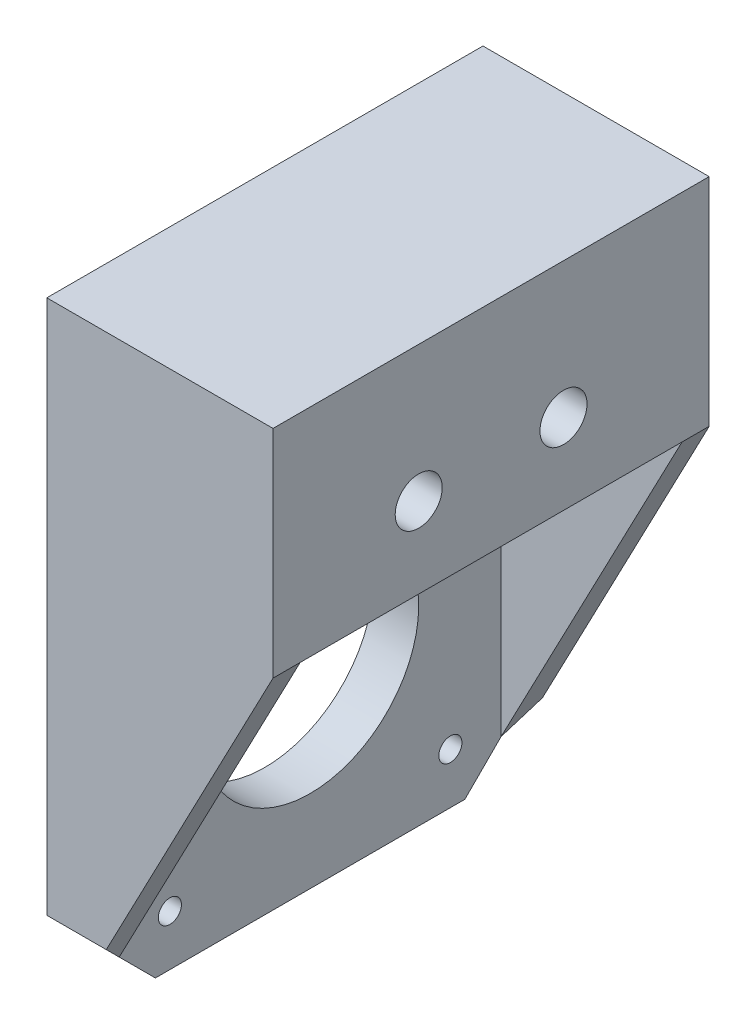
SolidWorks part; units mm, degrees
ref_plane "Front Plane" through (0, 0, 0) normal (0, 0, 1) x (1, 0, 0)
ref_plane "Top Plane" through (0, 0, 0) normal (0, 1, 0) x (1, 0, 0)
ref_plane "Right Plane" through (0, 0, 0) normal (1, 0, 0) x (0, 0, -1)
sketch "Sketch1" plane through (0, 0, 0) normal (1, 0, 0) x (0, 0, -1)
  line L0 (-0.3826, 8.0214) -> (-6.4826, 8.0214)
  line L1 (-6.4826, 8.0214) -> (-9.3826, 8.0214)
  line L2 (-9.3826, 8.0214) -> (-9.3826, -34.1786)
  line L3 (-9.3826, -34.1786) -> (-4.3816, -34.1786)
  line L4 (-4.3816, -34.1786) -> (-0.3826, -30.1796)
  line L5 (-0.3826, -30.1796) -> (-0.3826, 8.0214)
  line L6 (-6.4826, 25.8214) -> (-6.4826, 8.0214)
  line L7 (-6.4826, 8.0214) -> (-0.3826, 8.0214)
  line L8 (-0.3826, 8.0214) -> (2.6174, 8.0214)
  line L9 (2.6174, 8.0214) -> (2.6174, 25.8214)
  line L10 (2.6174, 25.8214) -> (-6.4826, 25.8214)
  circle A0 centre (-5.9826, -28.5786) radius 1.275
  circle A1 centre (-5.9826, 2.4214) radius 1.275
extrude "Boss-Extrude1" add sketch "Sketch1" along normal blind 5 contours L4 L5 L0 L1 L2 L3 A1 A0 | L9 L10 L6 L0 L8 region at (0, -12.6414, 4.9216) region at (0, 16.9214, 1.9326)
sketch "Sketch2" plane through (5, 0, 0) normal (1, 0, 0) x (0, 0, -1)
  line L1 (-6.4826, 25.8214) -> (2.6174, 25.8214)
  line L2 (-6.4826, 25.8214) -> (-6.4826, 8.0214)
  line L3 (-6.4826, 8.0214) -> (2.6174, 8.0214)
  line L4 (2.6174, 25.8214) -> (2.6174, 8.0214)
extrude "Boss-Extrude2" add sketch "Sketch2" along normal blind 20
sketch "Sketch3" plane through (0, 0, 0.3826) normal (0, 0, -1) x (-1, 0, 0)
  line L1 (-25, 8.0214) -> (0, 8.0214)
  line L2 (0, 8.0214) -> (0, -30.1796)
  line L3 (0, -30.1796) -> (-5, -30.1796)
  line L4 (-5, -30.1796) -> (-25, 8.0214)
extrude "Boss-Extrude3" add sketch "Sketch3" along normal blind 3
sketch "Sketch4" plane through (5, 0, 0) normal (1, 0, 0) x (0, 0, -1)
  line L0 (-0.3826, -30.1796) -> (2.6174, -27.1796)
  line L1 (2.6174, 8.0214) -> (2.6174, -30.1796) construction
  line L2 (2.6174, -27.1796) -> (2.6174, -30.1796)
  line L3 (2.6174, -30.1796) -> (-0.3826, -30.1796)
extrude "Cut-Extrude1" cut sketch "Sketch4" against normal mid plane 30
ref_plane "Plane2" through (0, 0, 21.4826) normal (0, 0, 1) x (1, 0, 0)
mirror "Mirror14" about plane through (0, 0, 21.4826) normal (0, 0, 1) of bodies 104 106
sketch "Sketch7" plane through (5, 0, 0) normal (1, 0, 0) x (0, 0, -1)
  line L1 (-33.5826, 8.0214) -> (-9.3826, 8.0214)
  line L2 (-33.5826, 8.0214) -> (-33.5826, -34.1786)
  line L3 (-33.5826, -34.1786) -> (-9.3826, -34.1786)
  line L4 (-9.3826, 8.0214) -> (-9.3826, -34.1786)
extrude "Boss-Extrude4" add sketch "Sketch7" against normal blind 5
sketch "Sketch8" plane through (5, 0, 0) normal (1, 0, 0) x (0, 0, -1)
  circle A0 centre (-21.4826, -13.0786) radius 12
extrude "Cut-Extrude3" cut sketch "Sketch8" against normal blind 5
sketch "Sketch10" plane through (25, 0, 0) normal (1, 0, 0) x (0, 0, -1)
  line L1 (-45.5826, 25.8214) -> (2.6174, 25.8214)
  line L2 (-45.5826, 25.8214) -> (-45.5826, 8.0214)
  line L3 (-45.5826, 8.0214) -> (2.6174, 8.0214)
  line L4 (2.6174, 25.8214) -> (2.6174, 8.0214)
extrude "Boss-Extrude5" add sketch "Sketch10" against normal blind 5
fillet "Fillet1" radius 3 2 edges at (20, 16.9214, 36.4826) (20, 16.9214, 6.4826)
sketch "Sketch12" plane through (0, 25.8214, 0) normal (0, 1, 0) x (1, 0, 0)
  line L8 (25, 2.6174) -> (0, 2.6174)
  line L9 (0, 2.6174) -> (0, -6.4826)
  line L10 (0, -6.4826) -> (17, -6.4826)
  line L11 (20, -9.4826) -> (20, -33.4826)
  line L12 (17, -36.4826) -> (0, -36.4826)
  line L13 (0, -36.4826) -> (0, -45.5826)
  line L14 (0, -45.5826) -> (25, -45.5826)
  line L15 (25, -45.5826) -> (25, 2.6174)
  line L16 (25, 2.6174) -> (0, 2.6174)
  line L17 (0, 2.6174) -> (0, -6.4826)
  line L18 (0, -6.4826) -> (17, -6.4826)
  line L19 (20, -9.4826) -> (20, -33.4826)
  line L20 (17, -36.4826) -> (0, -36.4826)
  line L21 (0, -36.4826) -> (0, -45.5826)
  line L22 (0, -45.5826) -> (25, -45.5826)
  line L23 (25, -45.5826) -> (25, 2.6174)
  arc A2 (20, -9.4826) -> (17, -6.4826) centre (17, -9.4826) ccw
  arc A3 (17, -36.4826) -> (20, -33.4826) centre (17, -33.4826) ccw
  arc A4 (20, -9.4826) -> (17, -6.4826) centre (17, -9.4826) ccw
  arc A5 (17, -36.4826) -> (20, -33.4826) centre (17, -33.4826) ccw
  dimension "D1" = 0
extrude "Boss-Extrude6" add sketch "Sketch12" along normal blind 6.1
sketch "Sketch13" plane through (20, 0, 0) normal (-1, 0, 0) x (0, 0, 1)
  line L0 (21.4826, 31.9214) -> (21.4826, 16.9214)
  line L1 (9.4826, 31.9214) -> (33.4826, 31.9214) construction
  line L2 (21.4826, -9.35) -> (21.4826, 9.35) construction
  line L3 (21.4826, 16.9214) -> (29.4826, 16.9214)
  circle A0 centre (29.4826, 16.9214) radius 2.6
  circle A1 centre (13.4826, 16.9214) radius 2.6
extrude "Cut-Extrude4" cut sketch "Sketch13" against normal blind 16 contours A1 | A0 region at (20, 14.395, 29.4826) region at (20, 16.9214, 13.4826)
fillet "Fillet2" radius 3 2 edges at (2.5, 8.0214, 36.4826) (2.5, 8.0214, 6.4826)
sketch "Sketch14" plane through (0, 31.9214, 0) normal (0, 1, 0) x (1, 0, 0)
  line L1 (0, 2.6174) -> (25, 2.6174)
  line L2 (0, 2.6174) -> (0, -45.5826)
  line L3 (0, -45.5826) -> (25, -45.5826)
  line L4 (25, 2.6174) -> (25, -45.5826)
extrude "Boss-Extrude7" add sketch "Sketch14" against normal blind 5
